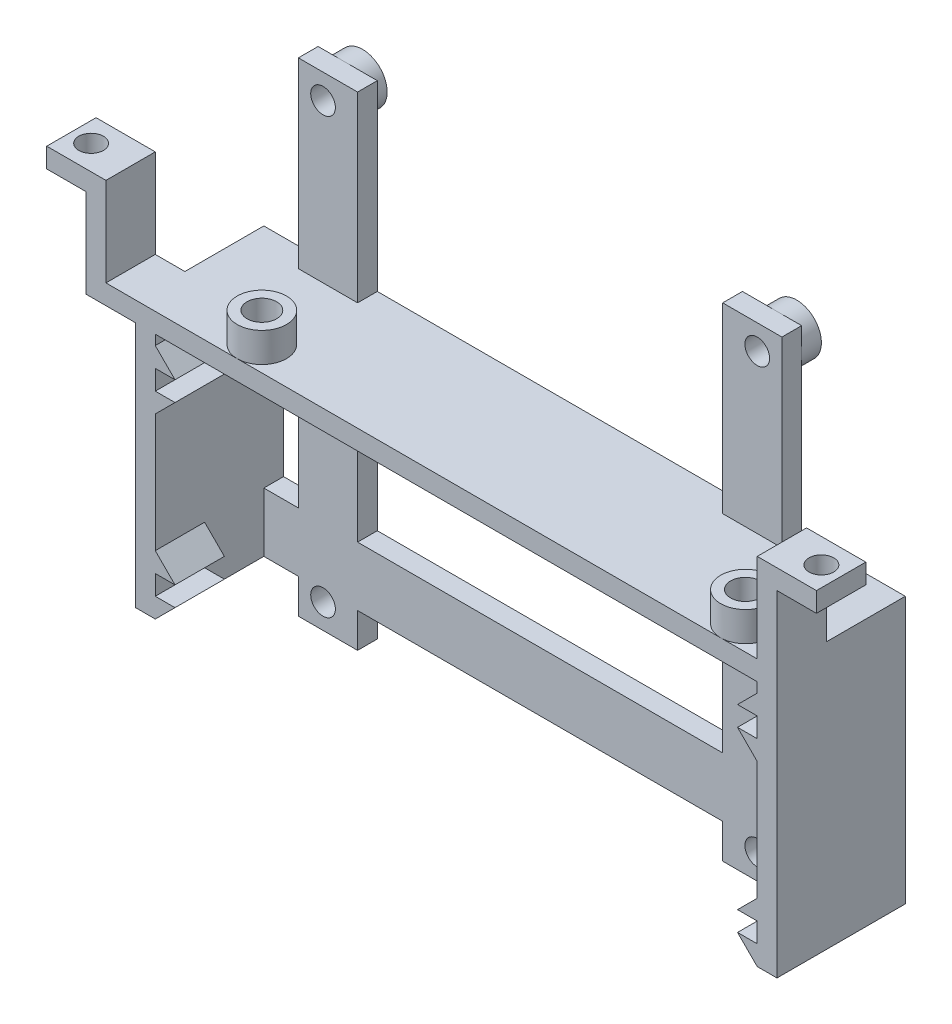
SolidWorks part; units mm, degrees
ref_plane "Front Plane" through (0, 0, 0) normal (0, 0, 1) x (1, 0, 0)
ref_plane "Top Plane" through (0, 0, 0) normal (0, 1, 0) x (1, 0, 0)
ref_plane "Right Plane" through (0, 0, 0) normal (1, 0, 0) x (0, 0, -1)
sketch "Sketch1" plane through (0, 0, 0) normal (0, 1, 0) x (1, 0, 0)
  line L1 (-33, 2.5) -> (33, 2.5)
  line L2 (-33, 2.5) -> (-33, -2.5)
  line L3 (-33, -2.5) -> (33, -2.5)
  line L4 (33, 2.5) -> (33, -2.5)
  line L5 (-33, 2.5) -> (33, -2.5) construction
  line L6 (-33, -2.5) -> (33, 2.5) construction
  point P0 (0, 0)
  dimension "D1" = 5
  dimension "D2" = 66
base flange "Base-Flange1" sketch "Sketch1" thickness 2 reverse thickness direction no parameters "D1"=4
sketch "Sketch2" plane through (0, 0, 0) normal (0, -1, 0) x (-1, 0, 0)
  line L0 (-29.3, -1.375) -> (-29.3, 1.375) construction
  line L1 (19.7, -1.375) -> (19.7, 1.375) construction
  line L2 (21.075, 0) -> (18.325, 0) construction
  circle A2 centre (19.7, 0) radius 2.5
  circle A3 centre (-29.3, 0) radius 2.5
  circle A4 centre (-29.3, 0) radius 1.375 construction
  circle A7 centre (19.7, 0) radius 1.375 construction
  point P15 (19.7, 0)
  dimension "D1" = 5
  dimension "D2" = 5
extrude "Boss-Extrude1" add sketch "Sketch2" against normal blind 3
sketch "Sketch3" plane through (0, -2, 0) normal (0, -1, 0) x (-1, 0, 0)
  line L1 (-33, -2.5) -> (-35, -2.5)
  line L2 (-33, -2.5) -> (-33, 2.5)
  line L3 (-33, 2.5) -> (-35, 2.5)
  line L4 (-35, -2.5) -> (-35, 2.5)
  line L5 (-34, 2.5) -> (-34, -2.5) construction
  line L6 (-33, 0) -> (-35, 0) construction
  point P184 (-34, 0)
  dimension "D1" = 2
extrude "Boss-Extrude2" add sketch "Sketch3" against normal blind 11
sketch "Sketch4" plane through (0, 9, 0) normal (0, 1, 0) x (1, 0, 0)
  line L1 (33, 2.5) -> (39, 2.5)
  line L2 (33, 2.5) -> (33, -2.5)
  line L3 (33, -2.5) -> (39, -2.5)
  line L4 (39, 2.5) -> (39, -2.5)
  line L5 (36, -2.5) -> (36, 2.5) construction
  line L6 (33, 0) -> (39, 0) construction
  point P120 (36, 0)
  dimension "D1" = 6
extrude "Boss-Extrude3" add sketch "Sketch4" against normal blind 2
mirror "Mirror1" about plane through (0, 0, 0) normal (1, 0, 0) of "Boss-Extrude3", "Boss-Extrude2"
sketch "Sketch5" plane through (0, 3, 0) normal (0, 1, 0) x (1, 0, 0)
  circle A0 centre (-19.7, 0) radius 1.5
  circle A1 centre (29.3, 0) radius 1.5
  dimension "D1" = 3
  dimension "D2" = 3
extrude "Cut-Extrude1" cut sketch "Sketch5" against normal through all normal cut yes
sketch "Sketch6" plane through (0, 9, 0) normal (0, 1, 0) x (1, 0, 0)
  line L0 (-39, 0) -> (-37, 0) construction
  line L1 (-39, -2.5) -> (-39, 2.5) construction
  line L2 (0, 0) -> (0, 18.8568) construction
  circle A0 centre (-37, 0) radius 1.25
  circle A1 centre (37, 0) radius 1.25
  dimension "D1" = 2.5
  dimension "D2" = 2
extrude "Cut-Extrude2" cut sketch "Sketch6" against normal through all normal cut yes
sketch "Sketch7" plane through (0, -2, 0) normal (0, -1, 0) x (-1, 0, 0)
  line L0 (35, -2.5) -> (-35, -2.5) construction
  line L1 (30, 2.5) -> (28, 2.5)
  line L2 (30, 2.5) -> (30, -2.5)
  line L3 (30, -2.5) -> (28, -2.5)
  line L4 (28, 2.5) -> (28, -2.5)
  line L5 (29, -2.5) -> (29, 2.5) construction
  line L6 (30, 0) -> (28, 0) construction
  line L7 (35, 2.5) -> (35, -2.5) construction
  point P104 (29, 0)
  dimension "D1" = 2
  dimension "D2" = 5
extrude "Boss-Extrude4" add sketch "Sketch7" along normal blind 25
sketch "Sketch8" plane through (0, 0, 2.5) normal (0, 0, 1) x (1, 0, 0)
  line L0 (-28, -3) -> (-26, -5)
  line L1 (-28, -27) -> (-28, -2) construction
  line L2 (-26, -5) -> (-28, -5)
  line L3 (-28, -5) -> (-28, -3)
  line L4 (-28, -2) -> (35, -2) construction
  line L5 (-28, -5) -> (-28, -7) construction
  line L6 (-28, -7) -> (-26, -7)
  line L7 (-26, -7) -> (-28, -9)
  line L8 (-28, -9) -> (-28, -7)
  line L9 (-28, -6) -> (-28, -24) construction
  line L10 (-28, -24) -> (-30.0471, -24) construction
  line L11 (-28, -15) -> (-20.8093, -15) construction
  line L12 (-28, -21) -> (-28, -23)
  line L13 (-26, -23) -> (-28, -21)
  line L14 (-28, -23) -> (-26, -23)
  line L15 (-28, -25) -> (-28, -27)
  line L16 (-28, -27) -> (-26, -25)
  line L17 (-26, -25) -> (-28, -25)
  point P15 (-28, -4)
  point P22 (-28, -26)
  dimension "D1" = 2
  dimension "D2" = 2
  dimension "D3" = 1
  dimension "D4" = 2
  dimension "D5" = 2
  dimension "D6" = 2
  dimension "D7" = 18
extrude "Boss-Extrude5" add sketch "Sketch8" against normal up to surface (5 mm away) up to face at (-5.9111, 0.1111, -2.5)
ref_plane "Plane1" through (2.5, 0, 0) normal (1, 0, 0) x (0, 0, -1)
mirror "Mirror2" about plane through (2.5, 0, 0) normal (1, 0, 0) of "Boss-Extrude5", "Boss-Extrude4"
sketch "Sketch11" plane through (0, 0, -2.5) normal (0, 0, 1) x (1, 0, 0)
  line L0 (-30, -27) -> (-30, 0)
  line L1 (-33, 0) -> (-19.7, 0) construction
  line L2 (-30, 0) -> (35, 0)
  line L3 (35, 7) -> (35, -27) construction
  line L4 (35, 0) -> (35, -27)
  line L5 (35, -27) -> (33, -27)
  line L6 (33, -27) -> (33, -2)
  line L7 (33, -2) -> (-28, -2)
  line L8 (-28, -2) -> (-28, -27)
  line L9 (-28, -27) -> (-30, -27)
extrude "Boss-Extrude6" add sketch "Sketch11" against normal blind 8
sketch "Sketch13" plane through (0, 0, -10.5) normal (0, 0, -1) x (-1, 0, 0)
  line L0 (-35, -27) -> (-35, 0) construction
  line L1 (30, -27) -> (-35, -27)
  line L2 (30, -27) -> (30, -21)
  line L3 (30, -21) -> (-35, -21)
  line L4 (-35, -27) -> (-35, -21)
  line L5 (-2.5, -21) -> (-2.5, -27) construction
  line L6 (30, -24) -> (-35, -24) construction
  point P168 (-2.5, -24)
  dimension "D1" = 6
extrude "Boss-Extrude8" add sketch "Sketch13" against normal blind 2
sketch "Sketch12" plane through (0, 0, -10.5) normal (0, 0, -1) x (-1, 0, 0)
  line L0 (0, 0) -> (0, -6) construction
  line L2 (-24.5, 18.5) -> (-24.5, -30.5)
  line L4 (24.5, 18.5) -> (24.5, -30.5)
  line L5 (0, -38.5) -> (0, 16.5) construction
  line L6 (-24.5, -6) -> (24.5, -6) construction
  line L7 (-33, 9) -> (-39, 9) construction
  line L8 (-24.5, 18.5) -> (-18.5, 18.5)
  line L9 (-18.5, 18.5) -> (-18.5, -30.5)
  line L10 (-18.5, -30.5) -> (-24.5, -30.5)
  line L11 (24.5, 18.5) -> (18.5, 18.5)
  line L12 (18.5, 18.5) -> (18.5, -30.5)
  line L13 (18.5, -30.5) -> (24.5, -30.5)
  line L14 (18.5, 18.5) -> (-18.5, 18.5) construction
  point P13 (0, -6)
  point P92 (0, -6)
  dimension "D1" = 49
  dimension "D2" = 49
  dimension "D3" = 15
  dimension "D4" = 6
  dimension "D5" = 6
extrude "Boss-Extrude7" add sketch "Sketch12" against normal blind 2
sketch "Sketch14" plane through (0, 0, -10.5) normal (0, 0, -1) x (-1, 0, 0)
  line L5 (-22, 18.5) -> (-22, 13.5) construction
  line L12 (0, 0) -> (0, 18.5) construction
  line L13 (-22, -25.5) -> (-22, -30.5) construction
  line L21 (-24.5, 18.5) -> (-24.5, 0) construction
  line L22 (-18.5, 18.5) -> (-24.5, 18.5) construction
  line L27 (-24.5, -27) -> (-24.5, -30.5) construction
  line L28 (-24.5, -30.5) -> (-18.5, -30.5) construction
  circle A1 centre (-22, 16) radius 2.5
  circle A2 centre (22, 16) radius 2.5
  circle A3 centre (-22, -28) radius 2.5
  circle A4 centre (22, -28) radius 2.5
  point P5 (-24.5, 16)
  point P6 (-24.5, -27.9687)
  point P20 (-22, -30.5)
  point P23 (-24.5, -28)
  dimension "D1" = 5
  dimension "D2" = 5
extrude "Boss-Extrude9" add sketch "Sketch14" along normal blind 2
sketch "Sketch15" plane through (0, 0, -12.5) normal (0, 0, -1) x (-1, 0, 0)
  line L0 (-24.5, 16) -> (-22, 16) construction
  line L6 (24.5, -30.5) -> (-24.5, 18.5) construction
  line L7 (24.5, 18.5) -> (-24.5, -30.5) construction
  line L8 (0, -6) -> (0, 0) construction
  line L9 (0, -6) -> (-14.357, -6) construction
  line L10 (24.5, -30.5) -> (24.5, -28) construction
  circle A0 centre (-22, 16) radius 1.25
  circle A1 centre (22, 16) radius 1.25
  circle A2 centre (22, -28) radius 1.25
  circle A3 centre (-22, -28) radius 1.25
  point P0 (24.5, -30.5)
  point P2 (-21.7522, 15.7522)
  dimension "D1" = 2.5
extrude "Cut-Extrude3" cut sketch "Sketch15" against normal up to next
sketch "Bend-Lines1" [suppressed] plane through (0, 0, 0) normal (0, 1, 0) x (1, 0, 0)
sketch "Bounding-Box1" [suppressed] plane through (0, 0, 0) normal (0, 1, 0) x (1, 0, 0)
sheet metal parameters "Sheet-Metal1" thickness 2 parameters "D1"=4
flat pattern "Flat-Pattern1" [suppressed]
sketch "Bend-Lines2" plane through (0, 0, 0) normal (0, 1, 0) x (1, 0, 0)
sketch3d "Bounding-Box2" [suppressed]
  line L0 (33, -7.5, 0) -> (-33, -7.5, 0) construction
  line L1 (33, 7.5, 0) -> (-33, 7.5, 0) construction
  line L2 (33, -7.5, 0) -> (33, 7.5, 0) construction
  line L3 (-33, -7.5, 0) -> (-33, 7.5, 0) construction
sheet metal parameters "Sheet-Metal5" thickness 2 parameters "D1"=4
flat pattern "Flat-Pattern1"
sketch "Bend-Lines2" plane through (0, 0, 0) normal (0, 1, 0) x (1, 0, 0)
sketch3d "Bounding-Box2" [suppressed]
  line L0 (33, -2.5, 0) -> (-33, -2.5, 0) construction
  line L1 (33, 2.5, 0) -> (-33, 2.5, 0) construction
  line L2 (33, -2.5, 0) -> (33, 2.5, 0) construction
  line L3 (-33, -2.5, 0) -> (-33, 2.5, 0) construction
sheet metal parameters "Sheet-Metal6" thickness 2 parameters "D1"=4
flat pattern "Flat-Pattern1"
sketch "Bend-Lines2" plane through (0, 0, 0) normal (0, 1, 0) x (1, 0, 0)
sketch3d "Bounding-Box2" [suppressed]
  line L0 (33, -7.5, 0) -> (-33, -7.5, 0) construction
  line L1 (33, 7.5, 0) -> (-33, 7.5, 0) construction
  line L2 (33, -7.5, 0) -> (33, 7.5, 0) construction
  line L3 (-33, -7.5, 0) -> (-33, 7.5, 0) construction
sheet metal parameters "Sheet-Metal7" thickness 2 parameters "D1"=4
flat pattern "Flat-Pattern1"
sketch "Bend-Lines2" plane through (0, 0, 0) normal (0, 1, 0) x (1, 0, 0)
sketch3d "Bounding-Box2" [suppressed]
  line L0 (33, -2.5, 0) -> (-33, -2.5, 0) construction
  line L1 (33, 2.5, 0) -> (-33, 2.5, 0) construction
  line L2 (33, -2.5, 0) -> (33, 2.5, 0) construction
  line L3 (-33, -2.5, 0) -> (-33, 2.5, 0) construction
sheet metal parameters "Sheet-Metal8" thickness 2 parameters "D1"=4
flat pattern "Flat-Pattern1"
sketch "Bend-Lines2" plane through (0, 0, 0) normal (0, 1, 0) x (1, 0, 0)
sketch3d "Bounding-Box2" [suppressed]
  line L0 (33, -2.5, 0) -> (-33, -2.5, 0) construction
  line L1 (33, 2.5, 0) -> (-33, 2.5, 0) construction
  line L2 (33, -2.5, 0) -> (33, 2.5, 0) construction
  line L3 (-33, -2.5, 0) -> (-33, 2.5, 0) construction
sheet metal parameters "Sheet-Metal9" thickness 2 parameters "D1"=4
flat pattern "Flat-Pattern1"
sketch "Bend-Lines2" plane through (0, 0, 0) normal (0, 1, 0) x (1, 0, 0)
sketch3d "Bounding-Box2" [suppressed]
  line L0 (33, -2.5, 0) -> (-33, -2.5, 0) construction
  line L1 (33, 2.5, 0) -> (-33, 2.5, 0) construction
  line L2 (33, -2.5, 0) -> (33, 2.5, 0) construction
  line L3 (-33, -2.5, 0) -> (-33, 2.5, 0) construction
sheet metal parameters "Sheet-Metal10" thickness 2 parameters "D1"=4
flat pattern "Flat-Pattern1"
sketch "Bend-Lines2" plane through (0, 0, 0) normal (0, 1, 0) x (1, 0, 0)
sketch3d "Bounding-Box2" [suppressed]
  line L0 (33, -2.5, 0) -> (-33, -2.5, 0) construction
  line L1 (33, 2.5, 0) -> (-33, 2.5, 0) construction
  line L2 (33, -2.5, 0) -> (33, 2.5, 0) construction
  line L3 (-33, -2.5, 0) -> (-33, 2.5, 0) construction
sheet metal parameters "Sheet-Metal11" thickness 2 parameters "D1"=4
flat pattern "Flat-Pattern1"
sketch "Bend-Lines2" plane through (0, 0, 0) normal (0, 1, 0) x (1, 0, 0)
sketch3d "Bounding-Box2" [suppressed]
  line L0 (33, -2.5, 0) -> (-33, -2.5, 0) construction
  line L1 (33, 2.5, 0) -> (-33, 2.5, 0) construction
  line L2 (33, -2.5, 0) -> (33, 2.5, 0) construction
  line L3 (-33, -2.5, 0) -> (-33, 2.5, 0) construction
sheet metal parameters "Sheet-Metal12" thickness 2 parameters "D1"=4
flat pattern "Flat-Pattern1"
sketch "Bend-Lines2" plane through (0, 0, 0) normal (0, 1, 0) x (1, 0, 0)
sketch3d "Bounding-Box2" [suppressed]
  line L0 (33, -2.5, 0) -> (-33, -2.5, 0) construction
  line L1 (33, 2.5, 0) -> (-33, 2.5, 0) construction
  line L2 (33, -2.5, 0) -> (33, 2.5, 0) construction
  line L3 (-33, -2.5, 0) -> (-33, 2.5, 0) construction
sheet metal parameters "Sheet-Metal14" thickness 2 parameters "D1"=4
flat pattern "Flat-Pattern1"
sketch "Bend-Lines2" plane through (0, 0, 0) normal (0, 1, 0) x (1, 0, 0)
sketch3d "Bounding-Box2" [suppressed]
  line L0 (33, -2.5, 0) -> (-33, -2.5, 0) construction
  line L1 (33, 2.5, 0) -> (-33, 2.5, 0) construction
  line L2 (33, -2.5, 0) -> (33, 2.5, 0) construction
  line L3 (-33, -2.5, 0) -> (-33, 2.5, 0) construction
sheet metal parameters "Sheet-Metal15" thickness 2 parameters "D1"=4
flat pattern "Flat-Pattern1"
sketch "Bend-Lines2" plane through (0, 0, 0) normal (0, 1, 0) x (1, 0, 0)
sketch3d "Bounding-Box2" [suppressed]
  line L0 (35, -2.5, 0) -> (-33, -2.5, 0) construction
  line L1 (35, 17.5, 0) -> (-33, 17.5, 0) construction
  line L2 (35, -2.5, 0) -> (35, 17.5, 0) construction
  line L3 (-33, -2.5, 0) -> (-33, 17.5, 0) construction
sheet metal parameters "Sheet-Metal16" thickness 2 parameters "D1"=4
flat pattern "Flat-Pattern1"
sketch "Bend-Lines2" plane through (0, 0, 0) normal (0, 1, 0) x (1, 0, 0)
sketch3d "Bounding-Box2" [suppressed]
  line L0 (35, -2.5, 0) -> (-33, -2.5, 0) construction
  line L1 (35, 17.5, 0) -> (-33, 17.5, 0) construction
  line L2 (35, -2.5, 0) -> (35, 17.5, 0) construction
  line L3 (-33, -2.5, 0) -> (-33, 17.5, 0) construction
sheet metal parameters "Sheet-Metal17" thickness 2 parameters "D1"=4
flat pattern "Flat-Pattern1"
sketch "Bend-Lines2" plane through (0, 0, 0) normal (0, 1, 0) x (1, 0, 0)
sketch3d "Bounding-Box2" [suppressed]
  line L0 (35, -2.5, 0) -> (-33, -2.5, 0) construction
  line L1 (35, 17.5, 0) -> (-33, 17.5, 0) construction
  line L2 (35, -2.5, 0) -> (35, 17.5, 0) construction
  line L3 (-33, -2.5, 0) -> (-33, 17.5, 0) construction
sheet metal parameters "Sheet-Metal18" thickness 2 parameters "D1"=4
flat pattern "Flat-Pattern1"
sketch "Bend-Lines2" plane through (0, 0, 0) normal (0, 1, 0) x (1, 0, 0)
sketch3d "Bounding-Box2" [suppressed]
  line L0 (35, -2.5, 0) -> (-33, -2.5, 0) construction
  line L1 (35, 17.5, 0) -> (-33, 17.5, 0) construction
  line L2 (35, -2.5, 0) -> (35, 17.5, 0) construction
  line L3 (-33, -2.5, 0) -> (-33, 17.5, 0) construction
sheet metal parameters "Sheet-Metal19" thickness 2 parameters "D1"=4
flat pattern "Flat-Pattern1"
sketch "Bend-Lines2" plane through (0, 0, 0) normal (0, 1, 0) x (1, 0, 0)
sketch3d "Bounding-Box2" [suppressed]
  line L0 (35, -2.5, 0) -> (-33, -2.5, 0) construction
  line L1 (35, 10.5, 0) -> (-33, 10.5, 0) construction
  line L2 (35, -2.5, 0) -> (35, 10.5, 0) construction
  line L3 (-33, -2.5, 0) -> (-33, 10.5, 0) construction
